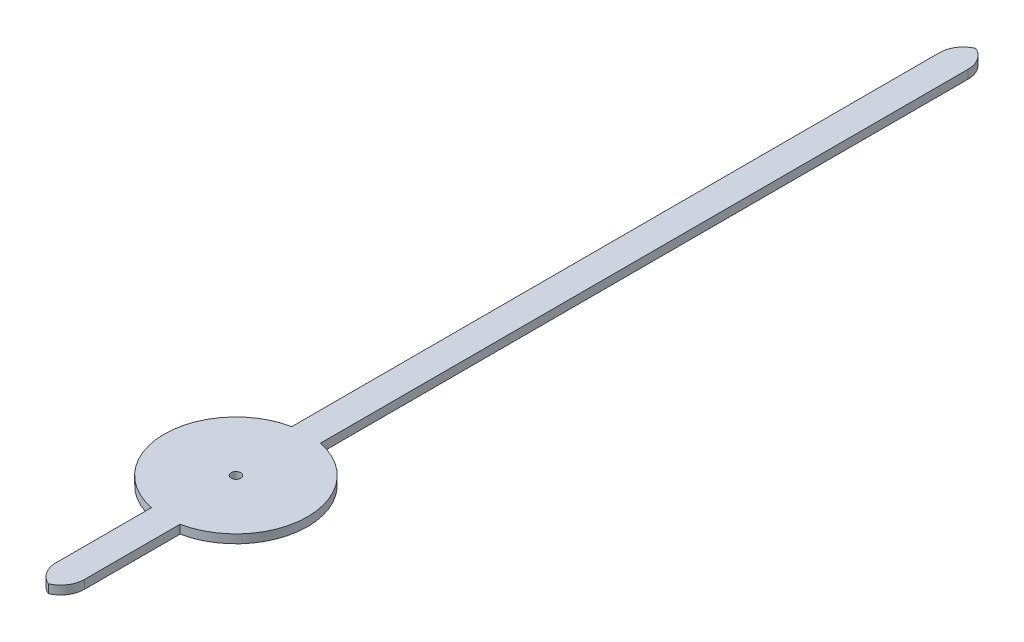
SolidWorks part; units mm, degrees
ref_plane "Front Plane" through (0, 0, 0) normal (0, 0, 1) x (1, 0, 0)
ref_plane "Top Plane" through (0, 0, 0) normal (0, 1, 0) x (1, 0, 0)
ref_plane "Right Plane" through (0, 0, 0) normal (1, 0, 0) x (0, 0, -1)
sketch "Sketch1" plane through (0, 0, 0) normal (0, 1, 0) x (1, 0, 0)
  line L0 (0, 0) -> (-0.1, 0) construction
  line L1 (-0.3, -3.9697) -> (-0.3, -1.4697)
  line L2 (0, -55) -> (0, 55) construction
  line L3 (0.3, -3.9697) -> (0.3, -1.4697)
  line L4 (-0.3, -3.9697) -> (0.3, -3.9697)
  line L5 (-0.3, 15.5303) -> (0.3, 15.5303)
  line L6 (-0.3, 1.4697) -> (-0.3, 15.5303)
  line L7 (0.3, 1.4697) -> (0.3, 15.5303)
  circle A0 centre (0, 0) radius 0.1
  arc A1 (-0.3, 1.4697) -> (-0.3, -1.4697) centre (0, 0) ccw
  arc A2 (0.3, -1.4697) -> (0.3, 1.4697) centre (0, 0) ccw
  dimension "D1" = 0.2
  dimension "D2" = 3
  dimension "D3" = 0.3
  dimension "D4" = 19.5
  dimension "D5" = 2.5
extrude "Boss-Extrude1" add sketch "Sketch1" along normal blind 0.18
fillet "Fillet2" radius 0.5 4 edges at (-0.3, 0.09, -15.5303) (0.3, 0.09, -15.5303) (-0.3, 0.09, 3.9697) (0.3, 0.09, 3.9697)
